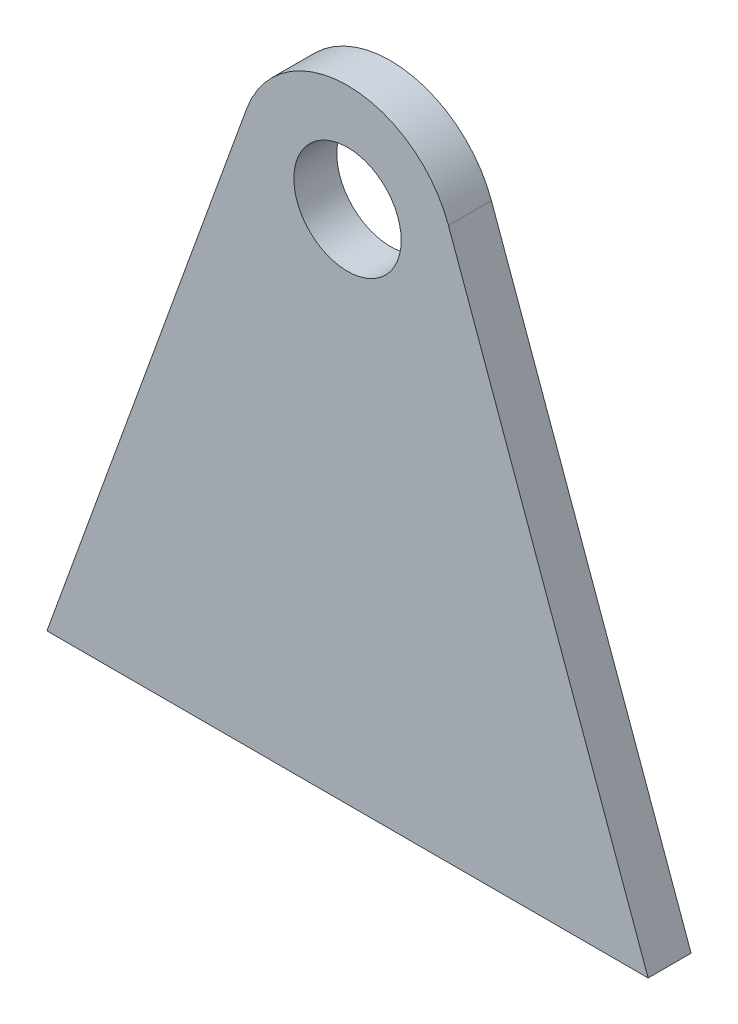
SolidWorks part; units mm, degrees
ref_plane "Front Plane" through (0, 0, 0) normal (0, 0, 1) x (1, 0, 0)
ref_plane "Top Plane" through (0, 0, 0) normal (0, 1, 0) x (1, 0, 0)
ref_plane "Right Plane" through (0, 0, 0) normal (1, 0, 0) x (0, 0, -1)
sketch "Sketch1" plane through (0, 0, 0) normal (0, 0, 1) x (1, 0, 0)
  line L1 (-140, -240) -> (140, -240)
  line L2 (-140, -240) -> (-47.0176, 17.0102)
  line L3 (140, -240) -> (47.0176, 17.0102)
  circle A0 centre (0, 0) radius 25
  arc A1 (47.0176, 17.0102) -> (-47.0176, 17.0102) centre (0, 0) ccw
  point P3 (0, 0)
  point P5 (0, 0)
  point P11 (0, 0)
  point P12 (0, 0)
  dimension "D1" = 50
  dimension "D2" = 50
  dimension "D3" = 280
  dimension "D4" = 240
extrude "Boss-Extrude1" add sketch "Sketch1" along normal blind 10 and the other way blind 10
